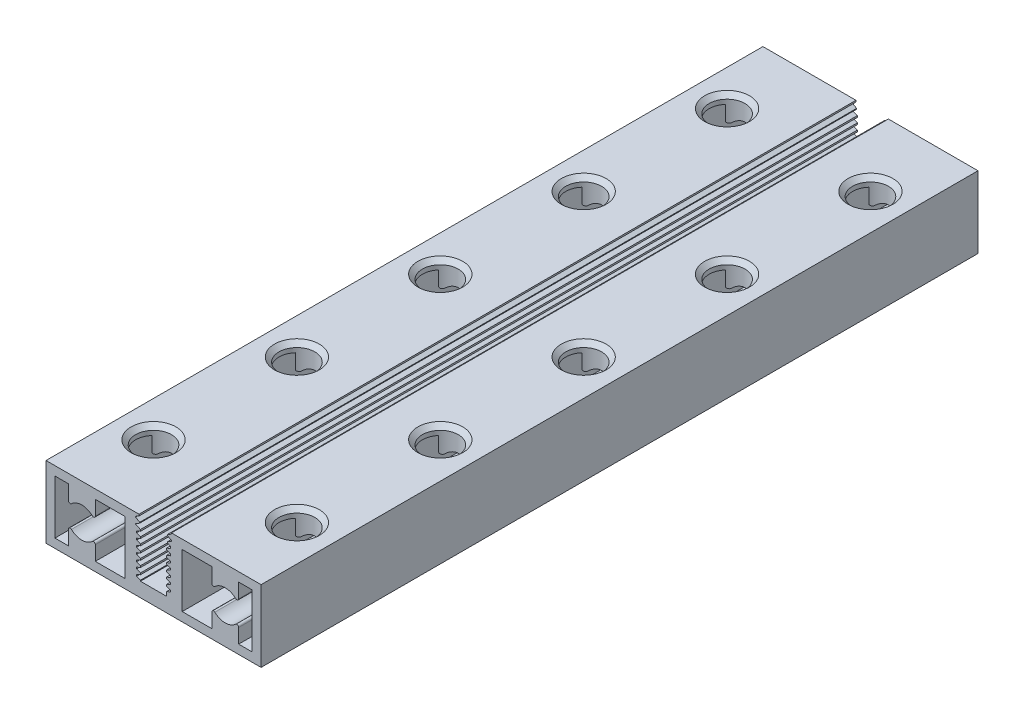
SolidWorks part; units mm, degrees
ref_plane "Front Plane" through (0, 0, 0) normal (0, 0, 1) x (1, 0, 0)
ref_plane "Top Plane" through (0, 0, 0) normal (0, 1, 0) x (1, 0, 0)
ref_plane "Right Plane" through (0, 0, 0) normal (1, 0, 0) x (0, 0, -1)
ref_plane "Plane1" through (0, 8, 0) normal (0, 1, 0) x (1, 0, 0)
sketch "Sketch1" plane through (0, 8, 0) normal (0, 1, 0) x (1, 0, 0)
  line L0 (12, -16) -> (-12, -16)
  line L1 (-12, -16) -> (-12, -96)
  line L2 (-12, -96) -> (12, -96)
  line L3 (12, -96) -> (12, -16)
extrude "Boss-Extrude1" add sketch "Sketch1" against normal blind 8
sketch "Sketch2" plane through (0, 0, 16) normal (0, 0, -1) x (-1, 0, 0)
  line L0 (1.62, 8) -> (-2, 8)
  line L1 (-2, 8) -> (-2, 7.88)
  line L2 (-2, 7.88) -> (-1.4684, 7.5731)
  line L3 (-1.4684, 7.5731) -> (-2.0747, 7.2231)
  line L4 (-2.0747, 7.2231) -> (-1.4684, 6.8731)
  line L5 (-1.4684, 6.8731) -> (-2.0878, 6.5155)
  line L6 (-2.0878, 6.5155) -> (-1.2404, 6.1731)
  line L7 (-1.2404, 6.1731) -> (-2.1067, 5.8231)
  line L8 (-2.1067, 5.8231) -> (-1.2404, 5.4731)
  line L9 (-1.2404, 5.4731) -> (-2.1067, 5.1231)
  line L10 (-2.1067, 5.1231) -> (-1.2404, 4.7731)
  line L11 (-1.2404, 4.7731) -> (-2.1067, 4.4231)
  line L12 (-2.1067, 4.4231) -> (-1.2404, 4.0731)
  line L13 (-1.2404, 4.0731) -> (-2.1067, 3.7231)
  line L14 (-2.1067, 3.7231) -> (-1.2404, 3.3731)
  line L15 (-1.2404, 3.3731) -> (-2.1067, 3.0231)
  line L16 (-2.1067, 3.0231) -> (-1.2404, 2.6731)
  line L17 (-1.2404, 2.6731) -> (-2.1067, 2.3231)
  line L18 (-2.1067, 2.3231) -> (-1.46, 2.0618)
  line L19 (-1.46, 2.0618) -> (-1.46, 1.6)
  line L20 (-1.46, 1.6) -> (1.46, 1.6)
  line L21 (1.46, 1.6) -> (1.46, 1.7012)
  line L22 (1.46, 1.7012) -> (2.1067, 1.9625)
  line L23 (2.1067, 1.9625) -> (1.2404, 2.3125)
  line L24 (1.2404, 2.3125) -> (2.1067, 2.6625)
  line L25 (2.1067, 2.6625) -> (1.2404, 3.0125)
  line L26 (1.2404, 3.0125) -> (2.1067, 3.3625)
  line L27 (2.1067, 3.3625) -> (1.2404, 3.7125)
  line L28 (1.2404, 3.7125) -> (2.1067, 4.0625)
  line L29 (2.1067, 4.0625) -> (1.2404, 4.4125)
  line L30 (1.2404, 4.4125) -> (2.1067, 4.7625)
  line L31 (2.1067, 4.7625) -> (1.2404, 5.1125)
  line L32 (1.2404, 5.1125) -> (2.1067, 5.4625)
  line L33 (2.1067, 5.4625) -> (1.2404, 5.8125)
  line L34 (1.2404, 5.8125) -> (2.1067, 6.1625)
  line L35 (2.1067, 6.1625) -> (1.2404, 6.5125)
  line L36 (1.2404, 6.5125) -> (2.0878, 6.8549)
  line L37 (2.0878, 6.8549) -> (1.4684, 7.2125)
  line L38 (1.4684, 7.2125) -> (2.0747, 7.5625)
  line L39 (2.0747, 7.5625) -> (1.62, 7.825)
  line L40 (1.62, 7.825) -> (1.62, 8)
extrude "Cut-Extrude1" cut sketch "Sketch2" against normal through all
sketch "Sketch3" plane through (0, 0, 96) normal (0, 0, 1) x (1, 0, 0)
  line L0 (9.5, 1) -> (11, 1)
  line L1 (11, 1) -> (11, 7)
  line L2 (11, 7) -> (9.5, 7)
  line L3 (9.5, 7) -> (9.5, 5.3856)
  line L4 (6.5, 5.3856) -> (6.5, 7)
  line L5 (6.5, 7) -> (3.2, 7)
  line L6 (3.2, 7) -> (3.2, 1)
  line L7 (3.2, 1) -> (6.5, 1)
  line L8 (6.5, 1) -> (6.5, 2.6144)
  line L9 (9.5, 2.6144) -> (9.5, 1)
  arc A0 (9.5, 5.3856) -> (9.1632, 5.2398) centre (9.3, 5.3856) cw
  arc A1 (9.1632, 5.2398) -> (6.8368, 5.2398) centre (8, 4) ccw
  arc A2 (6.8368, 5.2398) -> (6.5, 5.3856) centre (6.7, 5.3856) cw
  arc A3 (6.5, 2.6144) -> (6.8368, 2.7602) centre (6.7, 2.6144) cw
  arc A4 (6.8368, 2.7602) -> (9.1632, 2.7602) centre (8, 4) ccw
  arc A5 (9.1632, 2.7602) -> (9.5, 2.6144) centre (9.3, 2.6144) cw
extrude "Cut-Extrude2" cut sketch "Sketch3" against normal through all
sketch "Sketch4" plane through (0, 0, 16) normal (0, 0, -1) x (-1, 0, 0)
  line L0 (11, 7) -> (9.5, 7)
  line L1 (9.5, 7) -> (9.5, 5.3856)
  line L2 (6.5, 5.3856) -> (6.5, 7)
  line L3 (6.5, 7) -> (3.2, 7)
  line L4 (3.2, 7) -> (3.2, 1)
  line L5 (3.2, 1) -> (6.5, 1)
  line L6 (6.5, 1) -> (6.5, 2.6144)
  line L7 (9.5, 2.6144) -> (9.5, 1)
  line L8 (9.5, 1) -> (11, 1)
  line L9 (11, 1) -> (11, 7)
  arc A0 (9.5, 5.3856) -> (9.1632, 5.2398) centre (9.3, 5.3856) cw
  arc A1 (9.1632, 5.2398) -> (6.8368, 5.2398) centre (8, 4) ccw
  arc A2 (6.8368, 5.2398) -> (6.5, 5.3856) centre (6.7, 5.3856) cw
  arc A3 (6.5, 2.6144) -> (6.8368, 2.7602) centre (6.7, 2.6144) cw
  arc A4 (6.8368, 2.7602) -> (9.1632, 2.7602) centre (8, 4) ccw
  arc A5 (9.1632, 2.7602) -> (9.5, 2.6144) centre (9.3, 2.6144) cw
extrude "Cut-Extrude3" cut sketch "Sketch4" against normal through all
hole_wizard "Ø4.0 (4) Diameter Hole1" positions "Sketch6" profile "Sketch5" hole size "Ø4.0" standard "ANSI Metric"
sketch "Sketch6" plane through (0, 8, 0) normal (0, 1, 0) x (1, 0, 0)
  point P0 (-8, -88)
  point P1 (-8, -72)
  point P2 (-8, -56)
  point P3 (-8, -40)
  point P4 (-8, -24)
  point P5 (8, -40)
  point P6 (8, -56)
  point P7 (8, -24)
  point P8 (8, -72)
  point P9 (8, -88)
sketch "Sketch5" plane through (-8, 8, 88) normal (1, 0, 0) x (0, 0, 1)
  line L0 (0, 0) -> (0, 10.8144)
  line L1 (0, 10.8144) -> (2, 10.8144)
  line L2 (2, 10.8144) -> (2, 0)
  line L5 (2, 0) -> (0, 0)
  line L10 (0, 10.8144) -> (-2, 10.8144) construction
  line L11 (0, -6.35) -> (0, 107.95) construction
  dimension "Hole Dia." = 4
  dimension "Hole Depth" = 10.8144
  dimension "Drill Angle" = 180
chamfer "Chamfer1" distance 0.2368 angle 68 27 edges at (2.1067, 2.3231, 56) (2.1067, 5.1231, 56) (1.2404, 2.6731, 56) (-1.2404, 4.4125, 56) (1.2404, 4.7731, 56) (-1.2404, 5.1125, 56) (1.2404, 5.4731, 56) (-2.1067, 4.0625, 56) (2.1067, 4.4231, 56) (-2.1067, 5.4625, 56) (2.1067, 5.8231, 56) (-1.2404, 3.7125, 56) (1.2404, 4.0731, 56) (-2.1067, 4.7625, 56) (-1.2404, 5.8125, 56) (1.2404, 6.1731, 56) (-2.1067, 1.9625, 56) (-2.1067, 3.3625, 56) (2.1067, 3.7231, 56) (-2.1067, 6.1625, 56) (2.0878, 6.5155, 56) (-1.2404, 3.0125, 56) (1.2404, 3.3731, 56) (-1.2404, 6.5125, 56) (-2.1067, 2.6625, 56) (2.1067, 3.0231, 56) (-1.2404, 2.3125, 56) first distance on face at (1.7833, 2.1925, 56) first distance on face at (1.6736, 4.9481, 56) first distance on face at (1.6736, 2.4981, 56) first distance on face at (-1.6736, 4.5875, 56) first distance on face at (1.6736, 4.5981, 56) first distance on face at (-1.6736, 5.2875, 56) first distance on face at (1.6736, 5.2981, 56) first distance on face at (-1.6736, 3.8875, 56) first distance on face at (1.6736, 4.2481, 56) first distance on face at (1.6736, 5.6481, 56) first distance on face at (1.6736, 3.8981, 56) first distance on face at (-1.6736, 5.9875, 56) first distance on face at (1.6736, 5.9981, 56) first distance on face at (-1.7833, 1.8319, 56) first distance on face at (-1.6736, 3.1875, 56) first distance on face at (1.6736, 3.5481, 56) first distance on face at (1.6641, 6.3443, 56) first distance on face at (1.6736, 3.1981, 56) first distance on face at (-1.6641, 6.6837, 56) first distance on face at (-1.6736, 2.4875, 56) first distance on face at (1.6736, 2.8481, 56)
chamfer "Chamfer2" distance 0.0862 angle 60 6 edges at (1.4684, 7.5731, 56) (-1.4684, 7.2125, 56) (-2.0747, 7.5625, 56) (1.4684, 6.8731, 56) (-2.0878, 6.8549, 56) (2.0747, 7.2231, 56) first distance on face at (1.7342, 7.7266, 56) first distance on face at (-1.7716, 7.3875, 56) first distance on face at (-1.8473, 7.6938, 56) first distance on face at (1.7716, 7.0481, 56) first distance on face at (-1.7781, 7.0337, 56)
chamfer "Chamfer3" distance 0.5 angle 45 20 edges at (-8, 0, 58) (-8, 8, 42) (8, 8, 58) (-8, 0, 26) (-8, 0, 90) (8, 8, 26) (8, 8, 90) (-8, 8, 74) (-8, 0, 42) (-8, 0, 74) (8, 8, 42) (8, 8, 74) (-8, 8, 26) (-8, 8, 58) (-8, 8, 90) (8, 0, 26) (8, 0, 42) (8, 0, 58) (8, 0, 74) (8, 0, 90)
